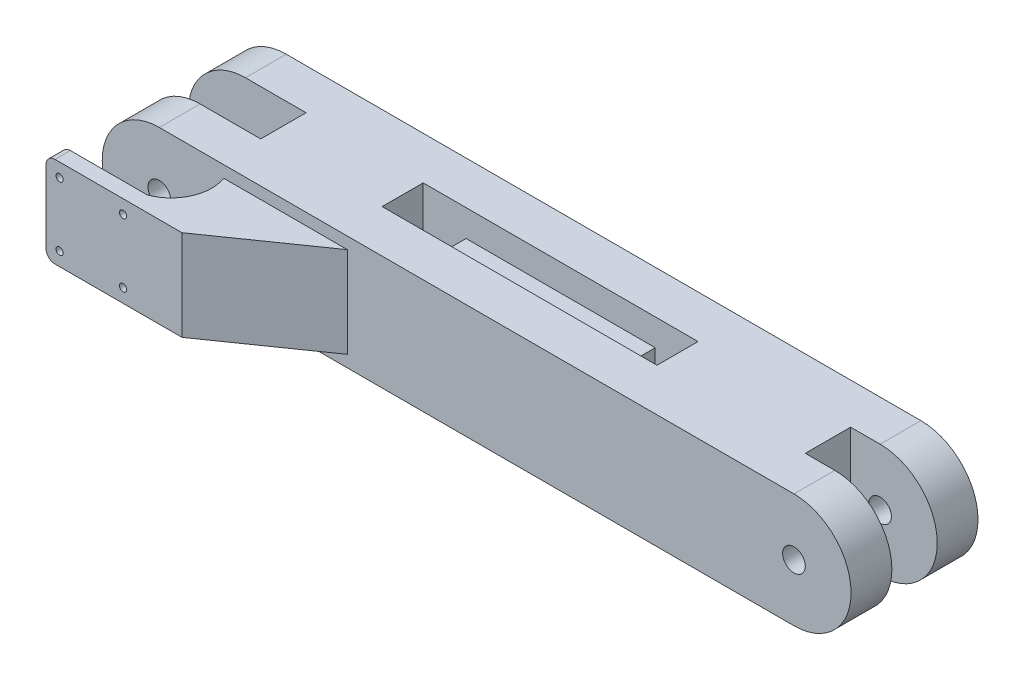
SolidWorks part; units mm, degrees
ref_plane "Front" through (0, 0, 0) normal (0, 0, 1) x (1, 0, 0)
ref_plane "Top" through (0, 0, 0) normal (0, 1, 0) x (1, 0, 0)
ref_plane "Right" through (0, 0, 0) normal (1, 0, 0) x (0, 0, -1)
sketch "Sketch1" plane through (0, 0, 0) normal (0, 0, 1) x (1, 0, 0)
  line L0 (-47.2174, -8.0761) -> (130.5826, -8.0761) construction
  line L1 (-47.2174, 7.9239) -> (130.5826, 7.9239)
  line L2 (-47.2174, -24.0761) -> (130.5826, -24.0761)
  arc A0 (-47.2174, 7.9239) -> (-47.2174, -24.0761) centre (-47.2174, -8.0761) ccw
  arc A1 (130.5826, -24.0761) -> (130.5826, 7.9239) centre (130.5826, -8.0761) ccw
  circle A2 centre (-47.2174, -8.0761) radius 3.175
  circle A3 centre (130.5826, -8.0761) radius 3.175
  point P2 (41.6826, -8.0761)
  dimension "D1" = 16
  dimension "D3" = 6.35
  dimension "D4" = 6.35
  dimension "D2" = 177.8
extrude "Boss-Extrude1" add sketch "Sketch1" along normal blind 11.43
sketch "Sketch2" plane through (0, 0, 11.43) normal (0, 0, 1) x (1, 0, 0)
  line L2 (-39.1367, -24.0761) -> (-39.1367, 7.9239)
  line L4 (130.5826, 7.9239) -> (-47.2174, 7.9239) construction
  line L7 (-47.2174, -24.0761) -> (130.5826, -24.0761) construction
  line L9 (122.3276, -24.0761) -> (122.3276, 7.9239)
  line L10 (-39.1367, 7.9239) -> (122.3276, 7.9239)
  line L11 (-39.1367, -24.0761) -> (122.3276, -24.0761)
  point P13 (-39.1367, -8.0761)
  point P16 (16.9972, 0.4239)
  point P24 (122.3276, -8.0761)
extrude "Boss-Extrude2" add sketch "Sketch2" along normal blind 12.7
sketch "Sketch5" plane through (0, 0, 24.13) normal (0, 0, 1) x (1, 0, 0)
  line L0 (-47.2174, -8.0761) -> (130.5826, -8.0761) construction
  line L1 (-47.2174, 7.9239) -> (130.5826, 7.9239)
  line L2 (-47.2174, -24.0761) -> (130.5826, -24.0761)
  arc A0 (-47.2174, 7.9239) -> (-47.2174, -24.0761) centre (-47.2174, -8.0761) ccw
  arc A1 (130.5826, -24.0761) -> (130.5826, 7.9239) centre (130.5826, -8.0761) ccw
  circle A2 centre (-47.2174, -8.0761) radius 3.175
  circle A3 centre (130.5826, -8.0761) radius 3.175
  point P4 (41.6826, -8.0761)
  dimension "D1" = 16
  dimension "D2" = 6.35
  dimension "D3" = 6.35
extrude "Boss-Extrude3" add sketch "Sketch5" along normal blind 11.43
sketch "Sketch6" plane through (0, 7.9239, 0) normal (0, 1, 0) x (1, 0, 0)
  line L0 (41.6826, 0) -> (41.6826, -35.56)
  line L1 (130.5826, 0) -> (-47.2174, 0) construction
  line L2 (130.5826, -35.56) -> (-47.2174, -35.56) construction
  line L3 (-39.1367, -17.78) -> (122.3276, -17.78)
  line L4 (-39.1367, -24.13) -> (-39.1367, -11.43) construction
  line L5 (122.3276, -24.13) -> (122.3276, -11.43) construction
  line L7 (3.1826, -23.53) -> (80.1826, -23.53)
  line L8 (3.1826, -23.53) -> (3.1826, -12.03)
  line L9 (3.1826, -12.03) -> (80.1826, -12.03)
  line L10 (80.1826, -23.53) -> (80.1826, -12.03)
  line L11 (3.1826, -23.53) -> (80.1826, -12.03) construction
  line L12 (3.1826, -12.03) -> (80.1826, -23.53) construction
  point P12 (41.6826, -17.78)
extrude "Cut-Extrude1" cut sketch "Sketch6" against normal blind 7.5 contours L7 L10 L9 L8
sketch "Sketch7" plane through (0, 0.4239, 0) normal (0, 1, 0) x (1, 0, 0)
  line L5 (3.1826, -23.53) -> (80.1826, -23.53) construction
  line L10 (3.1826, -12.03) -> (15.1826, -12.03)
  line L11 (3.1826, -12.03) -> (3.1826, -23.53)
  line L12 (3.1826, -23.53) -> (15.1826, -23.53)
  line L13 (15.1826, -12.03) -> (15.1826, -23.53)
  line L14 (3.1826, -12.03) -> (80.1826, -12.03) construction
  line L15 (80.1826, -23.53) -> (68.1826, -23.53)
  line L16 (80.1826, -23.53) -> (80.1826, -12.03)
  line L17 (80.1826, -12.03) -> (68.1826, -12.03)
  line L18 (68.1826, -23.53) -> (68.1826, -12.03)
sketch "Sketch10" plane through (0, 0, 35.56) normal (0, 0, 1) x (1, 0, 0)
  line L0 (-47.2174, -24.0761) -> (130.5826, -24.0761) construction
  line L1 (-34.5174, -20.7761) -> (-57.3774, -20.7761)
  line L3 (-34.5174, 4.6239) -> (-57.3774, 4.6239)
  line L4 (-59.9174, -18.2361) -> (-59.9174, 2.0839)
  line L5 (-34.5174, -20.7761) -> (-59.9174, 4.6239) construction
  line L6 (-34.5174, 4.6239) -> (-59.9174, -20.7761) construction
  line L7 (-34.5174, 4.6239) -> (-21.8174, 4.6239)
  line L9 (-34.5174, -20.7761) -> (-21.8174, -20.7761)
  line L10 (-21.8174, 4.6239) -> (-21.8174, -20.7761)
  arc A1 (-57.3774, -20.7761) -> (-59.9174, -18.2361) centre (-57.3774, -18.2361) cw
  arc A2 (-57.3774, 4.6239) -> (-59.9174, 2.0839) centre (-57.3774, 2.0839) ccw
  dimension "D1" = 2.54
  dimension "D2" = 35.56
  dimension "D3" = 25.4
  dimension "D4" = 12.7
  dimension "D5" = 3.3
extrude "Boss-Extrude4" add sketch "Sketch10" along normal blind 19.05 contours L4 A2 L3 L7 L10 L9 L1 A1
sketch "Sketch14" plane through (0, 4.6239, 0) normal (0, 1, 0) x (1, 0, 0)
  line L0 (-59.9174, -35.56) -> (-29.1834, -35.56)
  line L1 (-56.9493, -35.56) -> (-21.8174, -35.56) construction
  line L2 (-59.9174, -35.56) -> (-59.9174, -50.3102)
  line L3 (-59.9174, -54.61) -> (-59.9174, -35.56) construction
  line L4 (-59.9174, -50.3102) -> (-35.7956, -50.3102)
  arc A0 (-29.1834, -35.56) -> (-35.7956, -50.3102) centre (-39.8646, -39.629) cw
  dimension "D1" = 11.43
  dimension "D2" = 24.1218
  dimension "D3" = 14.7502
  dimension "D4" = 30.734
extrude "Cut-Extrude3" cut sketch "Sketch14" against normal blind 30.48
sketch "Sketch15" plane through (0, -20.7761, 0) normal (0, -1, 0) x (1, 0, 0)
  line L0 (-21.8174, 35.56) -> (5.4637, 35.56)
  line L1 (-47.2174, 35.56) -> (130.5826, 35.56) construction
  line L2 (-21.8174, 54.61) -> (5.4637, 35.56)
  line L3 (-21.8174, 54.61) -> (-21.8174, 35.56)
extrude "Boss-Extrude5" add sketch "Sketch15" against normal blind 25.4
extrude "Cut-Extrude4" cut sketch "Sketch7" against normal blind 50.8 contours L18 L17 L16 L15
extrude "Cut-Extrude5" cut sketch "Sketch7<5>" against normal blind 50.8 contours L13 L12 L11 L10
sketch "Sketch7<5>" plane through (0, 0.4239, 0) normal (0, 1, 0) x (1, 0, 0) same geometry as "Sketch7"
sketch "Sketch16" plane through (-39.1367, 0, 0) normal (-1, 0, 0) x (0, 0, 1)
  line L1 (11.43, 7.9239) -> (24.13, 7.9239)
  line L2 (11.43, 7.9239) -> (11.43, -24.0761)
  line L3 (11.43, -24.0761) -> (24.13, -24.0761)
  line L4 (24.13, 7.9239) -> (24.13, -24.0761)
extrude "Cut-Extrude6" cut sketch "Sketch16" against normal blind 8.89
sketch "Sketch17" plane through (0, 0, 50.3102) normal (0, 0, -1) x (-1, 0, 0)
  line L0 (47.2174, 4.6239) -> (47.2174, -20.7761) construction
  line L1 (57.3774, 4.6239) -> (35.7956, 4.6239) construction
  line L2 (35.7956, -20.7761) -> (57.3774, -20.7761) construction
  line L3 (35.7868, -8.0761) -> (59.9174, -8.0761) construction
  line L4 (59.9174, -18.2361) -> (59.9174, 2.0839) construction
  circle A0 centre (47.2174, -8.0761) radius 3.175 construction
  circle A1 centre (47.2174, -8.0761) radius 3.175
  circle A2 centre (56.1074, 0.8139) radius 1
  circle A3 centre (56.1074, -16.9661) radius 1
  circle A4 centre (38.3274, -16.9661) radius 1
  circle A5 centre (38.3274, 0.8139) radius 1
  dimension "D3" = 2
  dimension "D1" = 17.78
  dimension "D2" = 17.78
extrude "Cut-Extrude7" cut sketch "Sketch17" against normal up to surface (4.2998 mm away) contours A5 | A2 | A3 | A4 region at (-56.1074, 0.8139, 50.3102) region at (-56.1074, -16.9661, 50.3102) region at (-38.3274, 0.8139, 50.3102) up to face at (-46.5461, -8.0761, 54.61)
